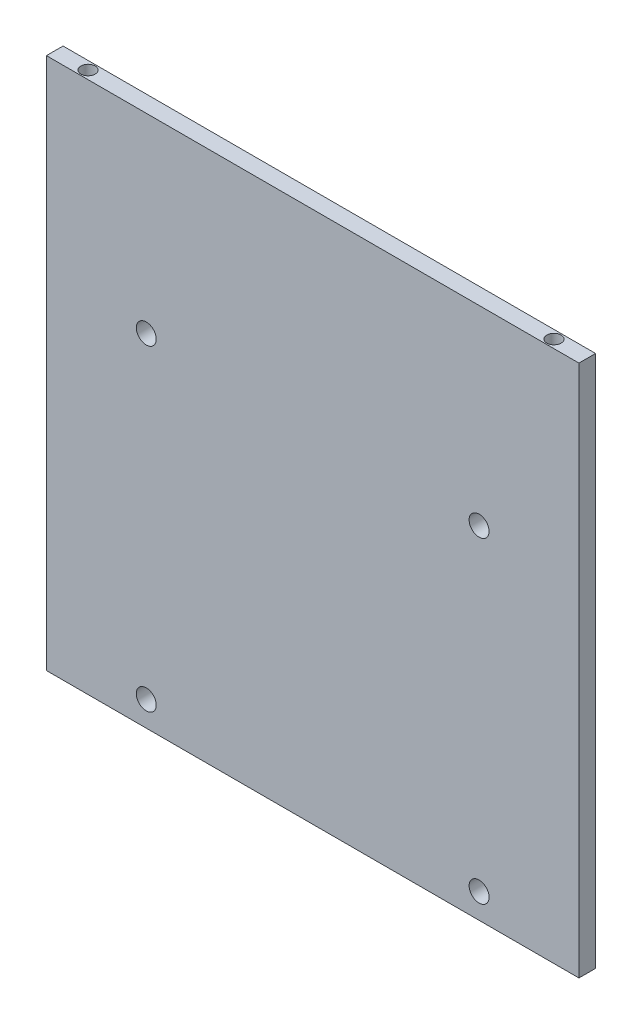
SolidWorks part; units mm, degrees
ref_plane "Front Plane" through (0, 0, 0) normal (0, 0, 1) x (1, 0, 0)
ref_plane "Top Plane" through (0, 0, 0) normal (0, 1, 0) x (1, 0, 0)
ref_plane "Right Plane" through (0, 0, 0) normal (1, 0, 0) x (0, 0, -1)
sketch "Sketch1" plane through (0, 0, 0) normal (0, 0, 1) x (1, 0, 0)
  line L1 (0, 0) -> (101.6, 0)
  line L2 (0, 0) -> (0, 101.6)
  line L3 (0, 101.6) -> (101.6, 101.6)
  line L4 (101.6, 0) -> (101.6, 101.6)
  dimension "D1" = 101.6
  dimension "D2" = 101.6
extrude "Boss-Extrude1" add sketch "Sketch1" along normal blind 3.175
sketch "Sketch4" plane through (0, 101.6, 0) normal (0, 1, 0) x (1, 0, 0)
  line L0 (0, -1.5875) -> (101.6, -1.5875) construction
  line L1 (0, -3.175) -> (0, 0) construction
  line L2 (101.6, -3.175) -> (101.6, 0) construction
  point P6 (6.35, -1.5875)
  point P7 (95.25, -1.5875)
  dimension "D1" = 6.35
  dimension "D2" = 6.35
hole_wizard "#6-32 Tapped Hole1" positions "Sketch5" profile "Sketch7" tap size "#6-32" standard "ANSI Inch"
sketch "Sketch5" plane through (0, 101.6, 0) normal (0, 1, 0) x (1, 0, 0)
  point P0 (95.25, -1.5875)
  point P4 (6.35, -1.5875)
sketch "Sketch7" plane through (95.25, 101.6, 1.5875) normal (1, 0, 0) x (0, 0, 1)
  line L0 (0, 0) -> (0, 15.7987)
  line L1 (0, 15.7987) -> (1.3525, 14.986)
  line L2 (1.3525, 14.986) -> (1.3525, 0)
  line L5 (1.3525, 0) -> (0, 0)
  line L10 (0, 15.7987) -> (-1.3526, 14.986) construction
  line L11 (0, -6.35) -> (0, 107.95) construction
  dimension "Tap Drill Dia." = 2.7051
  dimension "Tap Drill Depth" = 14.986
  dimension "Drill Angle" = 118
cosmetic thread "Hole Thread1" parameters "D1"=12.7, "D2"=3.5052
cosmetic thread "Hole Thread2" parameters "D1"=12.7, "D2"=3.5052
ref_point "Point1"
ref_point "Point2"
ref_axis "Axis1" through (0, 50.8, 1.5875) along (1, 0, 0)
ref_plane "Plane2" through (0, 50.8, 0) normal (0, -1, 0) x (1, 0, 0)
mirror "Mirror1" about plane through (0, 50.8, 0) normal (0, -1, 0) of "#6-32 Tapped Hole1"
sketch "Sketch8" plane through (0, 0, 0) normal (0, 0, 1) x (1, 0, 0)
  line L0 (50.8, 101.6) -> (50.8, 0) construction
  line L1 (0, 101.6) -> (101.6, 101.6) construction
  line L2 (0, 0) -> (101.6, 0) construction
  circle A0 centre (19.05, 65.2145) radius 1.905
  circle A1 centre (19.05, 4.7625) radius 1.905
  circle A2 centre (82.55, 4.7625) radius 1.905
  circle A3 centre (82.55, 65.2145) radius 1.905
  point P6 (19.05, 4.7625)
  point P7 (19.05, 65.2145)
  point P12 (82.55, 4.7625)
  point P13 (82.55, 65.2145)
  dimension "D4" = 3.81
  dimension "D1" = 60.452
  dimension "D2" = 31.75
  dimension "D3" = 4.7625
extrude "Cut-Extrude2" cut sketch "Sketch8" against normal up to next from surface starting at face at (50.8, 50.8, 3.175)
